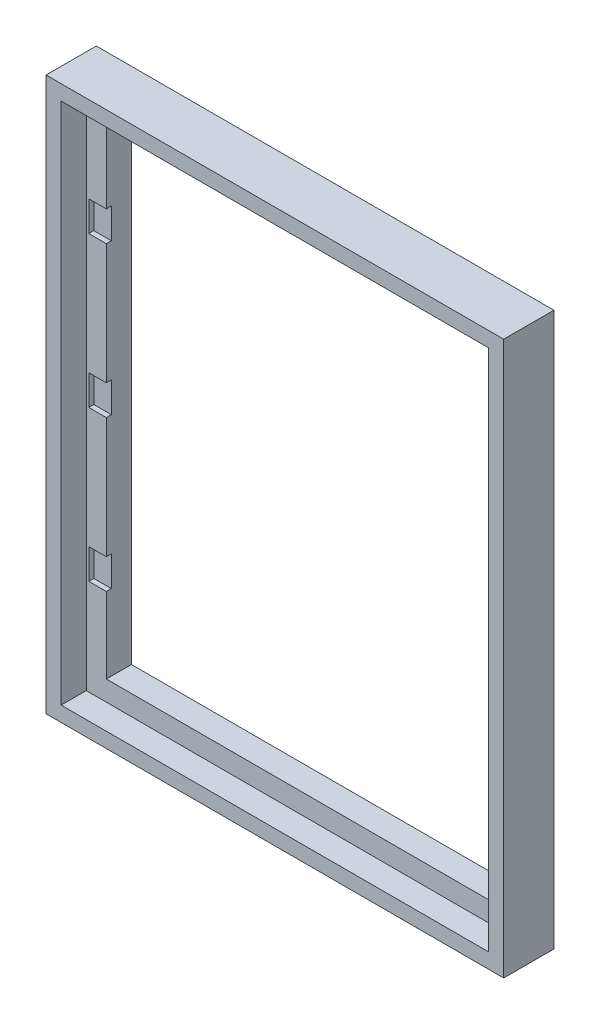
SolidWorks part; units mm, degrees
ref_plane "前视基准面" through (0, 0, 0) normal (0, 0, 1) x (1, 0, 0)
ref_plane "上视基准面" through (0, 0, 0) normal (0, 1, 0) x (1, 0, 0)
ref_plane "右视基准面" through (0, 0, 0) normal (1, 0, 0) x (0, 0, -1)
other "Configuration Table"
sketch "Model" plane through (0, 0, 0) normal (0, 0, 1) x (1, 0, 0)
  line L0 (-4.3804, 99.9831) -> (80.769, 99.9831)
  line L1 (80.769, -4.2164) -> (80.769, 99.9831)
  line L2 (-4.3804, -4.2164) -> (80.769, -4.2164)
  line L3 (-4.3804, -4.2164) -> (-4.3804, 99.9831)
  line L164 (-0.3804, 95.9831) -> (76.769, 95.9831)
  line L165 (-0.3804, -0.2164) -> (-0.3804, 95.9831)
  line L166 (-0.3804, -0.2164) -> (76.769, -0.2164)
  line L167 (76.769, -0.2164) -> (76.769, 95.9831)
  dimension "D1" = 77.1493
  dimension "D2" = 96.1995
  dimension "D3" = 4
extrude "凸台-拉伸2" add sketch "Model" along normal blind 5
sketch "草图2" plane through (0, 0, 5) normal (0, 0, 1) x (1, 0, 0)
  line L0 (-0.3804, 95.9831) -> (-0.3804, -0.2164) construction
  line L1 (-3.8804, 80.8834) -> (-0.3804, 80.8834)
  line L2 (-3.8804, 80.8834) -> (-3.8804, 74.8834)
  line L3 (-3.8804, 74.8834) -> (-0.3804, 74.8834)
  line L4 (-0.3804, 80.8834) -> (-0.3804, 74.8834)
  line L5 (-3.3804, 80.3834) -> (-0.3804, 80.3834) construction
  line L6 (-3.3804, 75.3834) -> (-3.3804, 80.3834) construction
  line L7 (-0.3804, 75.3834) -> (-3.3804, 75.3834) construction
  line L9 (76.769, 80.8834) -> (76.769, 74.8834)
  line L10 (80.269, 74.8834) -> (76.769, 74.8834)
  line L11 (80.269, 80.8834) -> (80.269, 74.8834)
  line L12 (80.269, 80.8834) -> (76.769, 80.8834)
  line L13 (-3.8804, 50.8834) -> (-0.3803, 50.8834)
  line L14 (-3.8804, 50.8834) -> (-3.8804, 44.8834)
  line L15 (-3.8804, 44.8834) -> (-0.3803, 44.8834)
  line L16 (-0.3803, 50.8834) -> (-0.3803, 44.8834)
  line L17 (76.769, 50.8834) -> (76.769, 44.8834)
  line L18 (80.269, 44.8834) -> (76.769, 44.8834)
  line L19 (80.269, 50.8834) -> (80.269, 44.8834)
  line L20 (80.269, 50.8834) -> (76.769, 50.8834)
  line L21 (-3.8804, 20.8834) -> (-0.3803, 20.8834)
  line L22 (-3.8804, 20.8834) -> (-3.8804, 14.8834)
  line L23 (-3.8804, 14.8834) -> (-0.3803, 14.8834)
  line L24 (-0.3803, 20.8834) -> (-0.3803, 14.8834)
  line L25 (76.769, 20.8834) -> (76.769, 14.8834)
  line L26 (80.269, 14.8834) -> (76.769, 14.8834)
  line L27 (80.269, 20.8834) -> (80.269, 14.8834)
  line L28 (80.269, 20.8834) -> (76.769, 20.8834)
  dimension "D1" = 0.5
  dimension "D2" = 0.5
  dimension "D3" = 0.5
extrude "切除-拉伸1" cut sketch "草图2" against normal blind 1
sketch "草图4" plane through (0, 0, 0) normal (0, 0, -1) x (-1, 0, 0)
  line L0 (-83.769, 102.9831) -> (-83.769, -7.2164)
  line L1 (-80.769, 99.9831) -> (4.3804, 99.9831)
  line L2 (-80.769, 99.9831) -> (-80.769, -4.2164)
  line L3 (-80.769, -4.2164) -> (4.3804, -4.2164)
  line L4 (4.3804, 99.9831) -> (4.3804, -4.2164)
  line L5 (-83.769, -7.2164) -> (7.3804, -7.2164)
  line L6 (7.3804, 102.9831) -> (7.3804, -7.2164)
  line L7 (-83.769, 102.9831) -> (7.3804, 102.9831)
  dimension "D1" = 3
extrude "凸台-拉伸5" add sketch "草图4" against normal blind 10
